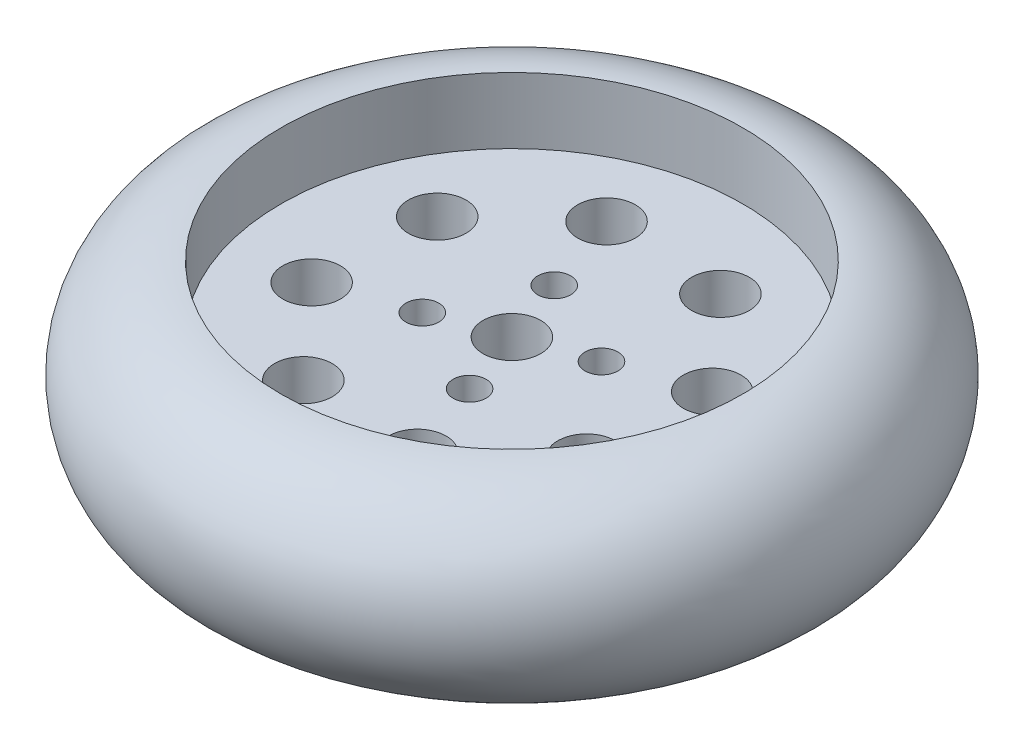
SolidWorks part; units mm, degrees
ref_plane "Plan de face" through (0, 0, 0) normal (0, 0, 1) x (1, 0, 0)
ref_plane "Plan de dessus" through (0, 0, 0) normal (0, 1, 0) x (1, 0, 0)
ref_plane "Plan de droite" through (0, 0, 0) normal (1, 0, 0) x (0, 0, -1)
sketch "Esquisse1" plane through (0, 0, 0) normal (0, 1, 0) x (1, 0, 0)
  circle A0 centre (0, 0) radius 40
  dimension "D1" = 80
extrude "Boss.-Extru.1" add sketch "Esquisse1" along normal blind 24
fillet "Congé2" 2 edges at (0, 24, 40) (0, 0, 40) type full round first side face at (0, 24, 40) second side face at (0, 0, 40) middle face at (0, 24, 40)
sketch "Esquisse2" plane through (0, 24, 0) normal (0, 1, 0) x (1, 0, 0)
  circle A0 centre (0, 0) radius 28 construction
  circle A1 centre (0, 0) radius 28
extrude "Enlèv. mat.-Extru.1" cut sketch "Esquisse2" against normal blind 8
sketch "Esquisse3" plane through (0, 0, 0) normal (0, -1, 0) x (1, 0, 0)
  circle A0 centre (0, 0) radius 28 construction
  circle A1 centre (0, 0) radius 28
extrude "Enlèv. mat.-Extru.2" cut sketch "Esquisse3" against normal blind 8
sketch "Esquisse4" plane through (0, 16, 0) normal (0, 1, 0) x (1, 0, 0)
  line L0 (0, 0) -> (-6.4085, 17.8866) construction
  circle A0 centre (0, 0) radius 3.5
  circle A1 centre (-2.867, 8.0019) radius 2
  circle A2 centre (8.0019, 2.867) radius 2
  circle A3 centre (2.867, -8.0019) radius 2
  circle A4 centre (-8.0019, -2.867) radius 2
  circle A5 centre (-6.4085, 17.8866) radius 3.5
  circle A6 centre (8.1162, 17.1793) radius 3.5
  circle A7 centre (17.8866, 6.4085) radius 3.5
  circle A8 centre (17.1793, -8.1162) radius 3.5
  circle A9 centre (6.4085, -17.8866) radius 3.5
  circle A10 centre (-8.1162, -17.1793) radius 3.5
  circle A11 centre (-17.8866, -6.4085) radius 3.5
  circle A12 centre (-17.1793, 8.1162) radius 3.5
  point P14 (0, 0)
  point P31 (0, 0)
  dimension "D1" = 7
  dimension "D2" = 4
  dimension "D5" = 7
  dimension "D3" = 8.5
  dimension "D6" = 10.5
  dimension "D4" = 4
  dimension "D7" = 8
extrude "Enlèv. mat.-Extru.3" cut sketch "Esquisse4" against normal through all
